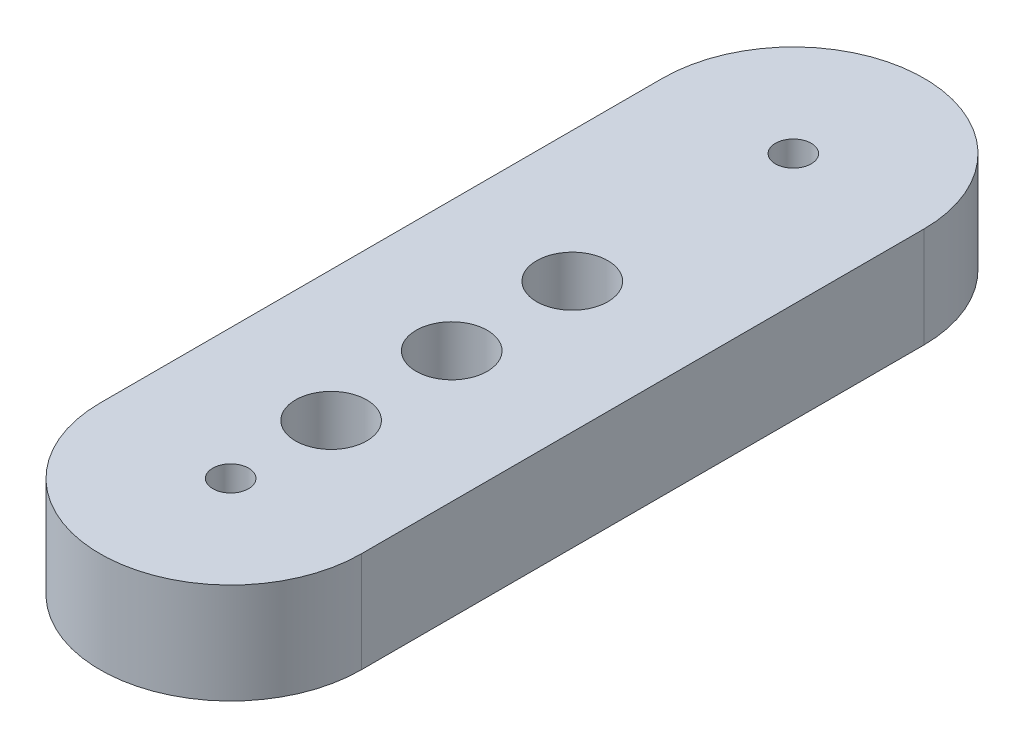
SolidWorks part; units mm, degrees
ref_plane "Front Plane" through (0, 0, 0) normal (0, 0, 1) x (1, 0, 0)
ref_plane "Top Plane" through (0, 0, 0) normal (0, 1, 0) x (1, 0, 0)
ref_plane "Right Plane" through (0, 0, 0) normal (1, 0, 0) x (0, 0, -1)
sketch "Sketch1" plane through (0, 0, 0) normal (0, 1, 0) x (1, 0, 0)
  line L0 (0, -17.78) -> (0, 17.78) construction
  line L1 (-8.255, -17.78) -> (-8.255, 17.78)
  line L2 (8.255, -17.78) -> (8.255, 17.78)
  arc A0 (-8.255, -17.78) -> (8.255, -17.78) centre (0, -17.78) ccw
  arc A1 (8.255, 17.78) -> (-8.255, 17.78) centre (0, 17.78) ccw
  circle A2 centre (0, 17.78) radius 1.1303
  circle A3 centre (0, -17.78) radius 1.1303
  circle A4 centre (0, -11.43) radius 2.25
  circle A5 centre (0, -3.81) radius 2.25
  circle A6 centre (0, 3.81) radius 2.25
  point P2 (0, 0)
  dimension "D3" = 2.2606
  dimension "D4" = 4.5
  dimension "D1" = 16.51
  dimension "D2" = 7.62
  dimension "D5" = 6.35
  dimension "D6" = 13.97
  dimension "D7" = 7.62
extrude "Boss-Extrude1" add sketch "Sketch1" along normal blind 6.35
